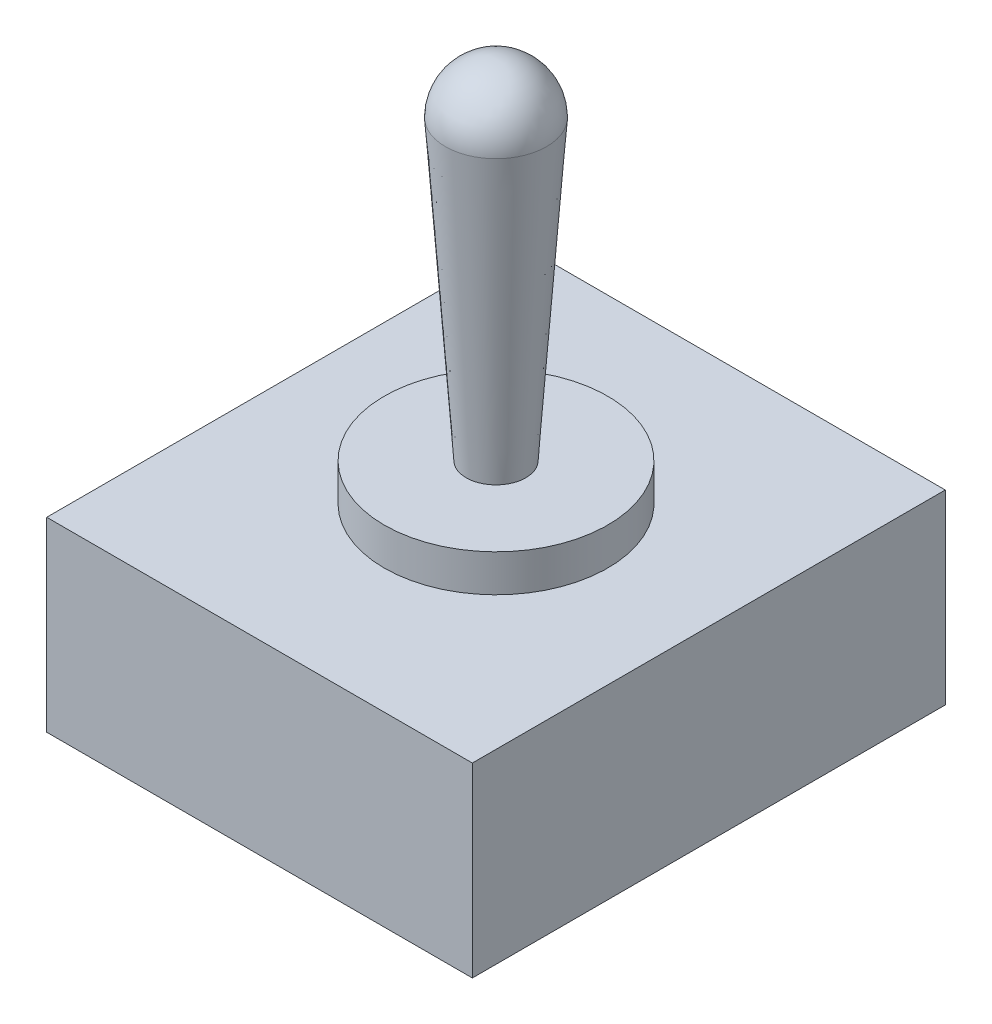
SolidWorks part; units mm, degrees
ref_plane "Front Plane" through (0, 0, 0) normal (0, 0, 1) x (1, 0, 0)
ref_plane "Top Plane" through (0, 0, 0) normal (0, 1, 0) x (1, 0, 0)
ref_plane "Right Plane" through (0, 0, 0) normal (1, 0, 0) x (0, 0, -1)
sketch "Sketch1" plane through (0, 0, 0) normal (0, 1, 0) x (1, 0, 0)
  line L1 (0, 0) -> (11.43, 0)
  line L2 (0, 0) -> (0, 12.7)
  line L3 (0, 12.7) -> (11.43, 12.7)
  line L4 (11.43, 0) -> (11.43, 12.7)
extrude "Boss-Extrude1" add sketch "Sketch1" along normal blind 5
sketch "Sketch2" plane through (0, 5, 0) normal (0, 1, 0) x (1, 0, 0)
  line L0 (0, 0) -> (11.43, 12.7)
  circle A0 centre (5.715, 6.35) radius 3
extrude "Boss-Extrude4" add sketch "Sketch2" along normal blind 1 contours L0 A0 | L0 A0 region at (4.7686, 5, -7.2018) region at (6.6614, 5, -5.4982)
ref_plane "Plane2" through (5.715, 0, 0) normal (-1, 0, 0) x (0, 0, 1)
sketch "Sketch3" plane through (5.715, 0, 0) normal (-1, 0, 0) x (0, 0, 1)
  line L0 (-3.35, 6) -> (-9.35, 6) construction
  line L1 (-7.15, 6) -> (-7.7081, 13.9805)
  line L2 (-5.55, 6) -> (-4.9919, 13.9805)
  line L3 (-7.7081, 13.9805) -> (-4.9919, 13.9805)
  line L4 (-6.35, 6) -> (-6.35, 13.9805)
  line L5 (-6.35, 13.9805) -> (-6.35, 15.3386)
  line L6 (-5.55, 6) -> (-7.15, 6)
  circle A0 centre (-6.35, 6) radius 0.8
  circle A1 centre (-6.35, 13.9805) radius 1.3581
revolve "Revolve3" add sketch "Sketch3" angle 360 about L4 region at (5.715, 9.9682, -6.9122) region at (5.715, 13.404, -6.9262) region at (5.715, 14.5569, -6.9264)
